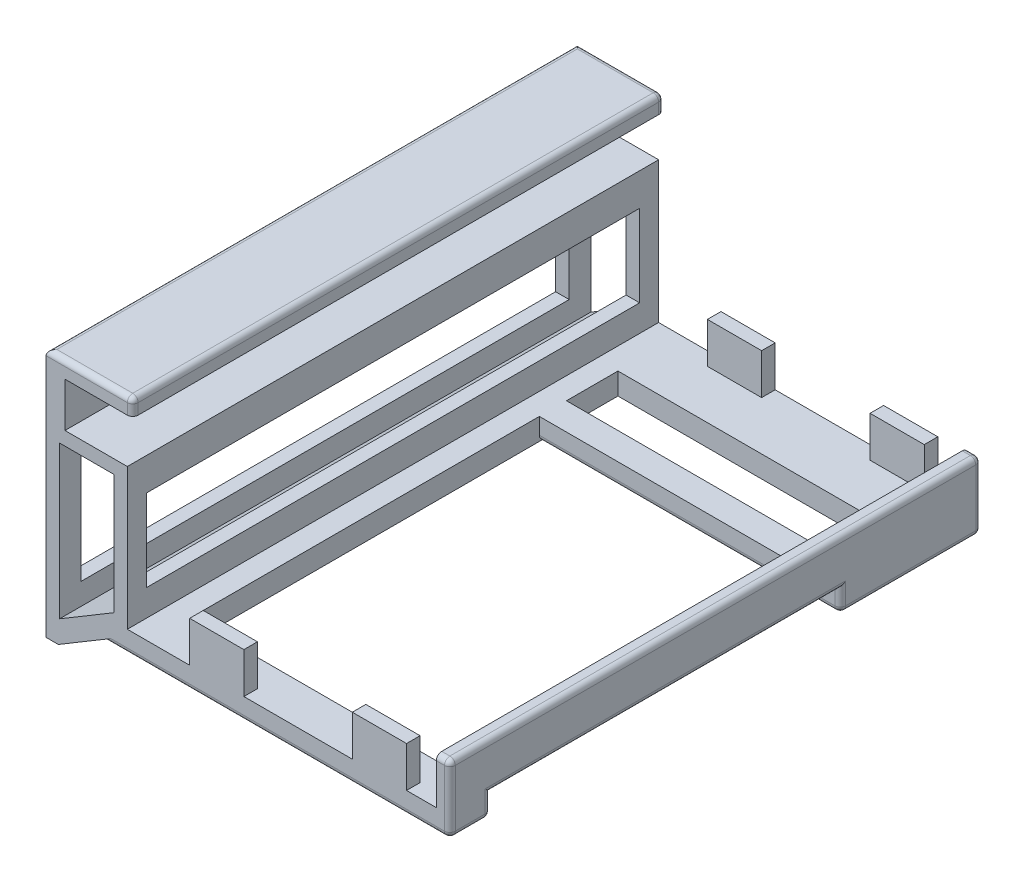
SolidWorks part; units mm, degrees
ref_plane "前视基准面" through (0, 0, 0) normal (0, 0, 1) x (1, 0, 0)
ref_plane "上视基准面" through (0, 0, 0) normal (0, 1, 0) x (1, 0, 0)
ref_plane "右视基准面" through (0, 0, 0) normal (1, 0, 0) x (0, 0, -1)
other "Configuration Table"
sketch "草图1" plane through (0, 0, 0) normal (0, 0, 1) x (1, 0, 0)
  line L0 (0, 0) -> (-23, 0)
  line L1 (-23, 0) -> (-23, 16.4)
  line L2 (-23, 16.4) -> (2, 16.4)
  line L3 (2, 16.4) -> (2, 22.4)
  line L4 (2, 22.4) -> (-30, 22.4)
  line L5 (-30, 22.4) -> (-30, -69.5935)
  line L6 (-30, -69.5935) -> (-25.4566, -69.5935)
  line L14 (114, -52) -> (0, -52)
  line L17 (0, -52) -> (0, 0)
  line L21 (119, -60) -> (-9.3982, -60)
  line L24 (-9.3982, -60) -> (-25.4566, -69.5935)
  line L26 (119, -60) -> (119, -35)
  line L27 (119, -35) -> (114, -35)
  line L28 (114, -35) -> (114, -52)
  point P8 (0, 0)
  point P10 (1.1541, -60)
  point P12 (0, 0)
  point P13 (-8.4395, -64.4578)
  dimension "D1" = 7
  dimension "D2" = 6
  dimension "D3" = 25
  dimension "D4" = 16.4
  dimension "D5" = 52
  dimension "D6" = 23
  dimension "D9" = 8
  dimension "D11" = 114
  dimension "D12" = 5
  dimension "D13" = 25
extrude "凸台-拉伸1" add sketch "草图1" along normal blind 196 contours L5 L6 L24 L21 L26 L27 L28 L14 L17 L0 L1 L2 L3 L4
sketch "草图2" plane through (0, 0, 196) normal (0, 0, 1) x (1, 0, 0)
  line L0 (-25, -5) -> (-25, -61.1667)
  line L1 (-25, -61.1667) -> (-5, -49.2184)
  line L2 (-5, -49.2184) -> (-5, -5)
  line L3 (-5, -5) -> (-25, -5)
  line L18 (2, 22.4) -> (-30, 22.4)
  line L19 (-30, 22.4) -> (-30, -69.5935)
  line L20 (-30, -69.5935) -> (-25.4566, -69.5935)
  line L21 (-25.4566, -69.5935) -> (-9.3982, -60)
  line L24 (-9.3982, -60) -> (119, -60)
  line L25 (119, -60) -> (119, -35)
  line L26 (119, -35) -> (114, -35)
  line L27 (114, -35) -> (114, -52)
  line L28 (114, -52) -> (0, -52)
  line L31 (0, -52) -> (0, 0)
  line L32 (0, 0) -> (-23, 0)
  line L33 (-23, 0) -> (-23, 16.4)
  line L34 (-23, 16.4) -> (2, 16.4)
  line L35 (2, 16.4) -> (2, 22.4)
  line L36 (2, 22.4) -> (-30, 22.4) construction
  line L37 (-30, 22.4) -> (-30, -69.5935) construction
  line L38 (-30, -69.5935) -> (-25.4566, -69.5935) construction
  line L39 (-25.4566, -69.5935) -> (-9.3982, -60) construction
  line L42 (-9.3982, -60) -> (119, -60) construction
  line L43 (119, -60) -> (119, -35) construction
  line L44 (119, -35) -> (114, -35) construction
  line L45 (114, -35) -> (114, -52) construction
  line L46 (114, -52) -> (0, -52) construction
  line L49 (0, -52) -> (0, 0) construction
  line L50 (0, 0) -> (-23, 0) construction
  line L51 (-23, 0) -> (-23, 16.4) construction
  line L52 (-23, 16.4) -> (2, 16.4) construction
  line L53 (2, 16.4) -> (2, 22.4) construction
  point P6 (-11.5, 0)
  dimension "D2" = 5
  dimension "D3" = 5
  dimension "D4" = 5
  dimension "D5" = 7
  dimension "D1" = 0
extrude "切除-拉伸1" cut sketch "草图2" against normal through all contours L3 L0 L1 L2
sketch "草图4" plane through (0, -52, 0) normal (0, 1, 0) x (1, 0, 0)
  line L0 (8, -23) -> (114, -23)
  line L1 (114, -23) -> (114, -42)
  line L2 (114, -42) -> (8, -42)
  line L4 (114, 0) -> (0, 0)
  line L5 (0, 0) -> (0, -196)
  line L6 (0, -196) -> (114, -196)
  line L7 (114, -196) -> (114, 0)
  line L8 (114, 0) -> (0, 0) construction
  line L10 (0, -196) -> (114, -196) construction
  line L11 (114, -196) -> (114, 0) construction
  line L13 (8, 0) -> (8, -196) construction
  line L14 (8, -23) -> (8, -42)
  line L19 (0, 0) -> (0, -196)
  point P10 (0, 0)
  point P11 (0, 0)
  point P12 (0, 0)
  dimension "D2" = 23
  dimension "D3" = 42
  dimension "D4" = 8
  dimension "D1" = 0
extrude "切除-拉伸2" cut sketch "草图4" against normal through all contours L0 L1 L2 L14
sketch "草图6" plane through (0, -52, 0) normal (0, 1, 0) x (1, 0, 0)
  line L0 (8, -52) -> (8, -181)
  line L1 (8, -181) -> (114, -181)
  line L2 (114, -181) -> (114, -52)
  line L3 (114, -52) -> (8, -52)
  line L8 (8, -23) -> (114, -23)
  line L9 (114, -23) -> (114, 0)
  line L10 (114, 0) -> (0, 0)
  line L11 (0, 0) -> (0, -196)
  line L12 (0, -196) -> (114, -196)
  line L13 (114, -196) -> (114, -42)
  line L14 (114, -42) -> (8, -42)
  line L15 (0, 0) -> (0, -196) construction
  line L16 (8, -23) -> (114, -23) construction
  line L17 (114, -23) -> (114, 0) construction
  line L18 (114, 0) -> (0, 0) construction
  line L20 (0, -196) -> (114, -196) construction
  line L21 (114, -196) -> (114, -42) construction
  line L22 (114, -42) -> (8, -42) construction
  line L28 (8, -42) -> (8, -23)
  line L29 (8, -42) -> (8, -23) construction
  dimension "D2" = 10
  dimension "D3" = 15
  dimension "D1" = 0
extrude "切除-拉伸3" cut sketch "草图6" against normal through all
sketch "草图7" plane through (0, -52, 0) normal (0, 1, 0) x (1, 0, 0)
  line L1 (114, -196) -> (0, -196) construction
  line L2 (23, -196) -> (43, -196)
  line L3 (23, -196) -> (23, -191)
  line L4 (23, -191) -> (43, -191)
  line L5 (43, -196) -> (43, -191)
  line L14 (23, -52) -> (23, -181)
  line L15 (23, -52) -> (23, -181) construction
  point P0 (25.2262, -204.5036)
  dimension "D1" = 5
  dimension "D2" = 20
  dimension "D3" = 15
extrude "凸台-拉伸3" add sketch "草图7" along normal blind 15 contours L4 L5 L2 L3
pattern_linear "阵列(线性)1" count 2 spacing 60 along (1, 0, 0) of "凸台-拉伸3"
sketch "草图10" plane through (-5, 0, 0) normal (-1, 0, 0) x (0, 0, 1)
  line L8 (189, -42.2184) -> (189, -12)
  line L9 (189, -12) -> (7, -12)
  line L10 (7, -12) -> (7, -42.2184)
  line L11 (7, -42.2184) -> (189, -42.2184)
  line L12 (189, -42.2184) -> (189, -12)
  line L13 (189, -12) -> (7, -12)
  line L14 (7, -12) -> (7, -42.2184)
  line L15 (7, -42.2184) -> (189, -42.2184)
  dimension "D1" = 7
extrude "切除-拉伸6" cut sketch "草图10" against normal up to next
sketch "草图12" plane through (-25, 0, 0) normal (1, 0, 0) x (0, 0, -1)
  line L8 (-188, -13) -> (-188, -53.1667)
  line L9 (-188, -53.1667) -> (-8, -53.1667)
  line L10 (-8, -53.1667) -> (-8, -13)
  line L11 (-8, -13) -> (-188, -13)
  line L12 (-188, -13) -> (-188, -53.1667)
  line L13 (-188, -53.1667) -> (-8, -53.1667)
  line L14 (-8, -53.1667) -> (-8, -13)
  line L15 (-8, -13) -> (-188, -13)
  dimension "D1" = 8
extrude "切除-拉伸7" cut sketch "草图12" against normal up to next
sketch "草图13" plane through (114, 0, 0) normal (-1, 0, 0) x (0, 0, 1)
  line L0 (52, -52) -> (52, -60)
  line L1 (52, -60) -> (181, -60)
  line L2 (181, -60) -> (181, -52)
  line L3 (181, -52) -> (52, -52)
  line L12 (0, -35) -> (0, -52)
  line L13 (0, -52) -> (23, -52)
  line L14 (23, -52) -> (23, -60)
  line L15 (23, -60) -> (42, -60)
  line L16 (42, -60) -> (42, -52)
  line L17 (42, -52) -> (52, -52)
  line L18 (52, -52) -> (52, -60)
  line L19 (52, -60) -> (181, -60)
  line L20 (181, -60) -> (181, -52)
  line L21 (181, -52) -> (196, -52)
  line L22 (196, -52) -> (196, -35)
  line L23 (196, -35) -> (0, -35)
  line L24 (0, -35) -> (0, -52) construction
  line L25 (0, -52) -> (23, -52) construction
  line L26 (23, -52) -> (23, -60) construction
  line L27 (23, -60) -> (42, -60) construction
  line L28 (42, -60) -> (42, -52) construction
  line L29 (42, -52) -> (52, -52) construction
  line L30 (52, -52) -> (52, -60) construction
  line L31 (52, -60) -> (181, -60) construction
  line L32 (181, -60) -> (181, -52) construction
  line L33 (181, -52) -> (196, -52) construction
  line L34 (196, -52) -> (196, -35) construction
  line L35 (196, -35) -> (0, -35) construction
  dimension "D1" = 0
extrude "切除-拉伸8" cut sketch "草图13" against normal up to next
sketch "草图14" plane through (0, -52, 0) normal (0, 1, 0) x (1, 0, 0)
  line L0 (114, 0) -> (0, 0) construction
  line L1 (23, 0) -> (43, 0)
  line L2 (23, 0) -> (23, -5)
  line L3 (23, -5) -> (43, -5)
  line L4 (43, 0) -> (43, -5)
  line L5 (43, -196) -> (43, -191) construction
  line L7 (23, -191) -> (43, -191) construction
  line L9 (43, -196) -> (43, -191) construction
  line L11 (23, -191) -> (43, -191) construction
  line L12 (23, -195) -> (23, -191) construction
  point P9 (0, 0)
  dimension "D1" = 5
extrude "凸台-拉伸4" add sketch "草图14" along normal blind 15
pattern_linear "阵列(线性)2" count 2 spacing 60 along (1, 0, 0) of "凸台-拉伸4"
fillet "圆角1" radius 2 6 edges at (2, 19.4, 0) (2, 19.4, 196) (-14, 22.4, 0) (2, 22.4, 98) (-14, 22.4, 196) (-30, 22.4, 98)
fillet "圆角2" radius 2 6 edges at (54.8009, -60, 196) (119, -47.5, 196) (54.8009, -60, 0) (119, -47.5, 0) (119, -60, 26) (119, -60, 188.5)
fillet "圆角3" radius 2 6 edges at (115.5, -35, 196) (118.4142, -35, 195.4142) (115.5, -35, 0) (118.4142, -35, 0.5858) (119, -52, 116.5) (119, -35, 98)
fillet "圆角4" radius 2 6 edges at (62.5, -60, 52) (118.4142, -59.4142, 52) (62.5, -60, 181) (118.4142, -59.4142, 181) (119, -54, 52) (119, -54, 181)
